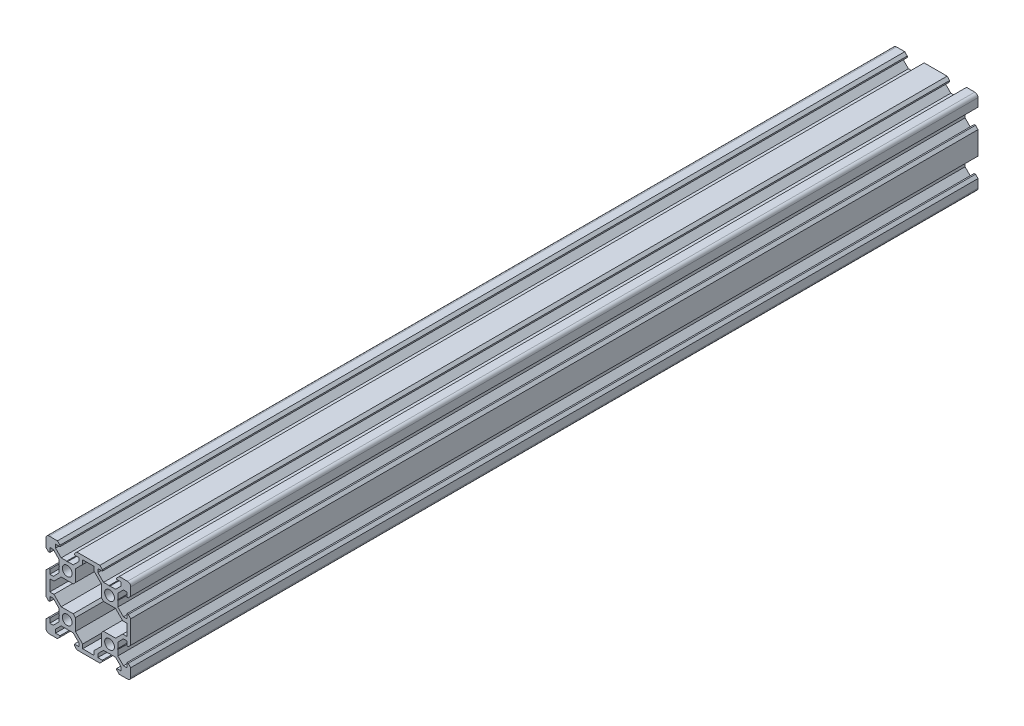
SolidWorks part; units mm, degrees
material "6061-T6 (SS)"
ref_plane "Front Plane" through (0, 0, 0) normal (0, 0, 1) x (1, 0, 0)
ref_plane "Top Plane" through (0, 0, 0) normal (0, 1, 0) x (1, 0, 0)
ref_plane "Right Plane" through (0, 0, 0) normal (1, 0, 0) x (0, 0, -1)
sketch "Sketch1" plane through (0, 0, 0) normal (0, 0, 1) x (1, 0, 0)
  line L1 (18.5, -20) -> (-18.5, -20)
  line L2 (20, -18.5) -> (20, 18.5)
  line L3 (18.5, 20) -> (-18.5, 20)
  line L4 (-20, -18.5) -> (-20, 18.5)
  line L5 (20, -20) -> (-20, 20) construction
  line L6 (20, 20) -> (-20, -20) construction
  circle A0 centre (-10, 10) radius 2.3
  circle A1 centre (10, -10) radius 2.3
  circle A2 centre (10, 10) radius 2.3
  circle A3 centre (-10, -10) radius 2.3
  arc A4 (-18.5, -20) -> (-20, -18.5) centre (-18.5, -18.5) cw
  arc A5 (18.5, -20) -> (20, -18.5) centre (18.5, -18.5) ccw
  arc A6 (20, 18.5) -> (18.5, 20) centre (18.5, 18.5) ccw
  arc A7 (-18.5, 20) -> (-20, 18.5) centre (-18.5, 18.5) ccw
  point P0 (0, 0)
  line B0 (-10, 10) -> (-10, 20) construction
  line B1 (-10, 13.69) -> (-10.21, 13.9)
  line B2 (-10.21, 13.9) -> (-12.8393, 13.9)
  line B3 (-12.8393, 13.9) -> (-15.5, 16.5607)
  line B4 (-15.5, 16.5607) -> (-15.5, 18.2)
  line B5 (-15.5, 18.2) -> (-13.395, 18.2)
  line B6 (-13.395, 18.2) -> (-13.395, 18.815)
  line B7 (-13.395, 18.815) -> (-14.58, 20)
  line B8 (-14.58, 20) -> (-5.42, 20)
  line B9 (-10, 10) -> (-15.9132, 15.9132) construction
  line B10 (-6.605, 18.815) -> (-5.42, 20)
  line B11 (-6.605, 18.2) -> (-6.605, 18.815)
  line B12 (-4.5, 18.2) -> (-6.605, 18.2)
  line B13 (-4.5, 16.5607) -> (-4.5, 18.2)
  line B14 (-7.1607, 13.9) -> (-4.5, 16.5607)
  line B15 (-9.79, 13.9) -> (-7.1607, 13.9)
  line B16 (-10, 13.69) -> (-9.79, 13.9)
  line B17 (10, 10) -> (10, 20) construction
  line B18 (10, 13.69) -> (9.79, 13.9)
  line B19 (9.79, 13.9) -> (7.1607, 13.9)
  line B20 (7.1607, 13.9) -> (4.5, 16.5607)
  line B21 (4.5, 16.5607) -> (4.5, 18.2)
  line B22 (4.5, 18.2) -> (6.605, 18.2)
  line B23 (6.605, 18.2) -> (6.605, 18.815)
  line B24 (6.605, 18.815) -> (5.42, 20)
  line B25 (5.42, 20) -> (14.58, 20)
  line B26 (10, 10) -> (4.0868, 15.9132) construction
  line B27 (13.395, 18.815) -> (14.58, 20)
  line B28 (13.395, 18.2) -> (13.395, 18.815)
  line B29 (15.5, 18.2) -> (13.395, 18.2)
  line B30 (15.5, 16.5607) -> (15.5, 18.2)
  line B31 (12.8393, 13.9) -> (15.5, 16.5607)
  line B32 (10.21, 13.9) -> (12.8393, 13.9)
  line B33 (10, 13.69) -> (10.21, 13.9)
  line B34 (-10, 10) -> (-20, 10) construction
  line B35 (-13.69, 10) -> (-13.9, 9.79)
  line B36 (-13.9, 9.79) -> (-13.9, 7.1607)
  line B37 (-13.9, 7.1607) -> (-16.5607, 4.5)
  line B38 (-16.5607, 4.5) -> (-18.2, 4.5)
  line B39 (-18.2, 4.5) -> (-18.2, 6.605)
  line B40 (-18.2, 6.605) -> (-18.815, 6.605)
  line B41 (-18.815, 6.605) -> (-20, 5.42)
  line B42 (-20, 5.42) -> (-20, 14.58)
  line B43 (-10, 10) -> (-15.9132, 4.0868) construction
  line B44 (-18.815, 13.395) -> (-20, 14.58)
  line B45 (-18.2, 13.395) -> (-18.815, 13.395)
  line B46 (-18.2, 15.5) -> (-18.2, 13.395)
  line B47 (-16.5607, 15.5) -> (-18.2, 15.5)
  line B48 (-13.9, 12.8393) -> (-16.5607, 15.5)
  line B49 (-13.9, 10.21) -> (-13.9, 12.8393)
  line B50 (-13.69, 10) -> (-13.9, 10.21)
  line B51 (-10, -10) -> (-20, -10) construction
  line B52 (-13.69, -10) -> (-13.9, -10.21)
  line B53 (-13.9, -10.21) -> (-13.9, -12.8393)
  line B54 (-13.9, -12.8393) -> (-16.5607, -15.5)
  line B55 (-16.5607, -15.5) -> (-18.2, -15.5)
  line B56 (-18.2, -15.5) -> (-18.2, -13.395)
  line B57 (-18.2, -13.395) -> (-18.815, -13.395)
  line B58 (-18.815, -13.395) -> (-20, -14.58)
  line B59 (-20, -14.58) -> (-20, -5.42)
  line B60 (-10, -10) -> (-15.9132, -15.9132) construction
  line B61 (-18.815, -6.605) -> (-20, -5.42)
  line B62 (-18.2, -6.605) -> (-18.815, -6.605)
  line B63 (-18.2, -4.5) -> (-18.2, -6.605)
  line B64 (-16.5607, -4.5) -> (-18.2, -4.5)
  line B65 (-13.9, -7.1607) -> (-16.5607, -4.5)
  line B66 (-13.9, -9.79) -> (-13.9, -7.1607)
  line B67 (-13.69, -10) -> (-13.9, -9.79)
  line B68 (-10, -10) -> (-10, -20) construction
  line B69 (-10, -13.69) -> (-9.79, -13.9)
  line B70 (-9.79, -13.9) -> (-7.1607, -13.9)
  line B71 (-7.1607, -13.9) -> (-4.5, -16.5607)
  line B72 (-4.5, -16.5607) -> (-4.5, -18.2)
  line B73 (-4.5, -18.2) -> (-6.605, -18.2)
  line B74 (-6.605, -18.2) -> (-6.605, -18.815)
  line B75 (-6.605, -18.815) -> (-5.42, -20)
  line B76 (-5.42, -20) -> (-14.58, -20)
  line B77 (-10, -10) -> (-4.0868, -15.9132) construction
  line B78 (-13.395, -18.815) -> (-14.58, -20)
  line B79 (-13.395, -18.2) -> (-13.395, -18.815)
  line B80 (-15.5, -18.2) -> (-13.395, -18.2)
  line B81 (-15.5, -16.5607) -> (-15.5, -18.2)
  line B82 (-12.8393, -13.9) -> (-15.5, -16.5607)
  line B83 (-10.21, -13.9) -> (-12.8393, -13.9)
  line B84 (-10, -13.69) -> (-10.21, -13.9)
  line B85 (10, -10) -> (10, -20) construction
  line B86 (10, -13.69) -> (10.21, -13.9)
  line B87 (10.21, -13.9) -> (12.8393, -13.9)
  line B88 (12.8393, -13.9) -> (15.5, -16.5607)
  line B89 (15.5, -16.5607) -> (15.5, -18.2)
  line B90 (15.5, -18.2) -> (13.395, -18.2)
  line B91 (13.395, -18.2) -> (13.395, -18.815)
  line B92 (13.395, -18.815) -> (14.58, -20)
  line B93 (14.58, -20) -> (5.42, -20)
  line B94 (10, -10) -> (15.9132, -15.9132) construction
  line B95 (6.605, -18.815) -> (5.42, -20)
  line B96 (6.605, -18.2) -> (6.605, -18.815)
  line B97 (4.5, -18.2) -> (6.605, -18.2)
  line B98 (4.5, -16.5607) -> (4.5, -18.2)
  line B99 (7.1607, -13.9) -> (4.5, -16.5607)
  line B100 (9.79, -13.9) -> (7.1607, -13.9)
  line B101 (10, -13.69) -> (9.79, -13.9)
  line B102 (10, 10) -> (20, 10) construction
  line B103 (13.69, 10) -> (13.9, 10.21)
  line B104 (13.9, 10.21) -> (13.9, 12.8393)
  line B105 (13.9, 12.8393) -> (16.5607, 15.5)
  line B106 (16.5607, 15.5) -> (18.2, 15.5)
  line B107 (18.2, 15.5) -> (18.2, 13.395)
  line B108 (18.2, 13.395) -> (18.815, 13.395)
  line B109 (18.815, 13.395) -> (20, 14.58)
  line B110 (20, 14.58) -> (20, 5.42)
  line B111 (10, 10) -> (15.9132, 15.9132) construction
  line B112 (18.815, 6.605) -> (20, 5.42)
  line B113 (18.2, 6.605) -> (18.815, 6.605)
  line B114 (18.2, 4.5) -> (18.2, 6.605)
  line B115 (16.5607, 4.5) -> (18.2, 4.5)
  line B116 (13.9, 7.1607) -> (16.5607, 4.5)
  line B117 (13.9, 9.79) -> (13.9, 7.1607)
  line B118 (13.69, 10) -> (13.9, 9.79)
  line B119 (10, -10) -> (20, -10) construction
  line B120 (13.69, -10) -> (13.9, -9.79)
  line B121 (13.9, -9.79) -> (13.9, -7.1607)
  line B122 (13.9, -7.1607) -> (16.5607, -4.5)
  line B123 (16.5607, -4.5) -> (18.2, -4.5)
  line B124 (18.2, -4.5) -> (18.2, -6.605)
  line B125 (18.2, -6.605) -> (18.815, -6.605)
  line B126 (18.815, -6.605) -> (20, -5.42)
  line B127 (20, -5.42) -> (20, -14.58)
  line B128 (10, -10) -> (15.9132, -4.0868) construction
  line B129 (18.815, -13.395) -> (20, -14.58)
  line B130 (18.2, -13.395) -> (18.815, -13.395)
  line B131 (18.2, -15.5) -> (18.2, -13.395)
  line B132 (16.5607, -15.5) -> (18.2, -15.5)
  line B133 (13.9, -12.8393) -> (16.5607, -15.5)
  line B134 (13.9, -10.21) -> (13.9, -12.8393)
  line B135 (13.69, -10) -> (13.9, -10.21)
  line B136 (-18.2, -2.7) -> (-18.2, 2.7)
  line B137 (-18.2, 2.7) -> (-16.2393, 2.7)
  line B138 (-16.2393, 2.7) -> (-12.8393, 6.1)
  line B139 (-12.8393, 6.1) -> (-7.1607, 6.1)
  line B140 (-10, 6.1) -> (-10, 0) construction
  line B141 (-10, 0) -> (-18.2, 0) construction
  line B142 (-12.8393, -6.1) -> (-7.1607, -6.1)
  line B143 (-16.2393, -2.7) -> (-12.8393, -6.1)
  line B144 (-18.2, -2.7) -> (-16.2393, -2.7)
  line B145 (-10, 6.1) -> (-10, 10) construction
  line B146 (-10, 10) -> (-15.0927, 4.9073) construction
  line B147 (-10, 10) -> (-6.3747, 6.3747) construction
  line B148 (2.7, 18.2) -> (2.7, 16.2393)
  line B149 (2.7, 16.2393) -> (6.1, 12.8393)
  line B150 (6.1, 12.8393) -> (6.1, 7.1607)
  line B151 (-6.1, 12.8393) -> (-6.1, 7.1607)
  line B152 (-2.7, 16.2393) -> (-6.1, 12.8393)
  line B153 (-2.7, 18.2) -> (-2.7, 16.2393)
  line B154 (2.7, 18.2) -> (-2.7, 18.2)
  line B155 (2.7, -18.2) -> (-2.7, -18.2)
  line B156 (-2.7, -18.2) -> (-2.7, -16.2393)
  line B157 (-2.7, -16.2393) -> (-6.1, -12.8393)
  line B158 (-6.1, -12.8393) -> (-6.1, -7.1607)
  line B159 (6.1, -12.8393) -> (6.1, -7.1607)
  line B160 (2.7, -16.2393) -> (6.1, -12.8393)
  line B161 (2.7, -18.2) -> (2.7, -16.2393)
  line B162 (0, 18.2) -> (0, -18.2) construction
  line B163 (12.8393, -6.1) -> (7.1607, -6.1)
  line B164 (16.2393, -2.7) -> (12.8393, -6.1)
  line B165 (18.2, -2.7) -> (16.2393, -2.7)
  line B166 (18.2, -2.7) -> (18.2, 2.7)
  line B167 (18.2, 2.7) -> (16.2393, 2.7)
  line B168 (16.2393, 2.7) -> (12.8393, 6.1)
  line B169 (12.8393, 6.1) -> (7.1607, 6.1)
  line B170 (-7.1607, 6.1) -> (-6.1, 7.1607)
  line B171 (6.1, 7.1607) -> (7.1607, 6.1)
  line B172 (7.1607, -6.1) -> (6.1, -7.1607)
  line B173 (-6.1, -7.1607) -> (-7.1607, -6.1)
  dimension "D4" = 4.6
  dimension "D5" = 1.5
  dimension "D1" = 40
  dimension "D2" = 10
  dimension "D3" = 10
sketch_block_instance "V Slot 2-1"
sketch_block "V Slot 2" parameters "D1"=10, "D2"=11, "D3"=4.3, "D4"=1.8, "D5"=0.21, "D6"=45, "D7"=9.16, "D8"=1.5, "D9"=6.79
sketch_block_instance "V Slot 2-2"
sketch_block_instance "V Slot 2-3"
sketch_block_instance "V Slot 2-4"
sketch_block_instance "V Slot 2-5"
sketch_block_instance "V Slot 2-6"
sketch_block_instance "V Slot 2-7"
sketch_block_instance "V Slot 2-8"
sketch_block_instance "Center Cutout 2-1"
sketch_block "Center Cutout 2" parameters "D1"=5.4, "D2"=12.2, "D3"=8.2, "D4"=45, "D5"=10, "D6"=1.5
extrude "Boss-Extrude1" add sketch "Sketch1" along normal blind 400 contours B135 B120 B121 B122 B123 B124 B125 B126 L2 B112 B113 B114 B115 B116 B117 B118 B103 B104 B105 B106 B107 B108 B109 A6 L3 B27 B28 B29 B30 B31 B32 B33 B18 B19 B20 B21 B22 B23 B24 B10 B11 B12 B13 B14 B15 B16 B1 B2 B3 region at (16.54, -19.4343, 0)
